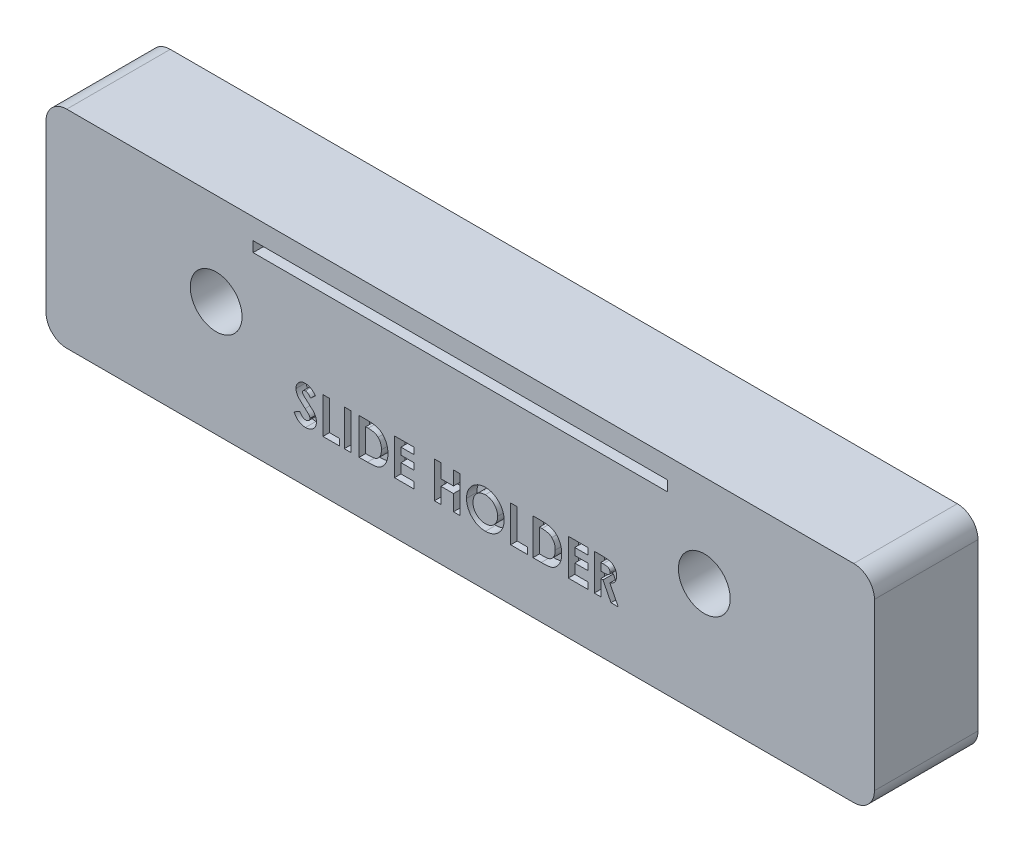
SolidWorks part; units mm, degrees
ref_plane "Front Plane" through (0, 0, 0) normal (0, 0, 1) x (1, 0, 0)
ref_plane "Top Plane" through (0, 0, 0) normal (0, 1, 0) x (1, 0, 0)
ref_plane "Right Plane" through (0, 0, 0) normal (1, 0, 0) x (0, 0, -1)
sketch "Sketch1" plane through (0, 0, 0) normal (0, 0, 1) x (1, 0, 0)
  line L1 (-40.3722, 21.485) -> (39.6278, 21.485)
  line L2 (-40.3722, 21.485) -> (-40.3722, 1.485)
  line L3 (-40.3722, 1.485) -> (39.6278, 1.485)
  line L4 (39.6278, 21.485) -> (39.6278, 1.485)
  dimension "D1" = 80
  dimension "D2" = 20
extrude "Boss-Extrude1" add sketch "Sketch1" along normal blind 10
sketch "Sketch2" plane through (0, 0, 10) normal (0, 0, 1) x (1, 0, 0)
  line L0 (39.6278, 21.485) -> (-40.3722, 21.485) construction
  line L1 (-40.3722, 21.485) -> (-40.3722, 1.485) construction
  line L2 (-0.3722, 21.485) -> (-0.3722, 1.485) construction
  line L3 (-40.3722, 1.485) -> (39.6278, 1.485) construction
  circle A0 centre (-23.9422, 12.585) radius 2.5
  circle A1 centre (23.1978, 12.585) radius 2.5
  dimension "D1" = 5
  dimension "D2" = 8.9
  dimension "D3" = 16.43
extrude "Cut-Extrude1" cut sketch "Sketch2" against normal blind 10
sketch "Sketch3" plane through (0, 0, 10) normal (0, 0, 1) x (1, 0, 0)
  line L0 (39.6278, 21.485) -> (-40.3722, 21.485) construction
  line L1 (-20.3722, 19.485) -> (19.6278, 19.485)
  line L2 (-20.3722, 19.485) -> (-20.3722, 18.485)
  line L3 (-20.3722, 18.485) -> (19.6278, 18.485)
  line L4 (19.6278, 19.485) -> (19.6278, 18.485)
  point P6 (-0.3722, 19.485)
  point P7 (-0.3722, 21.485)
  dimension "D1" = 1
  dimension "D2" = 2
  dimension "D3" = 40
extrude "Cut-Extrude2" cut sketch "Sketch3" against normal through all
sketch "Sketch4" plane through (0, 0, 10) normal (0, 0, 1) x (1, 0, 0)
  line L0 (-40.3722, 6.485) -> (39.6278, 6.485) construction
  line L1 (-40.3722, 21.485) -> (-40.3722, 1.485) construction
  line L3 (-40.3722, 1.485) -> (39.6278, 1.485) construction
  line L4 (39.6278, 1.485) -> (39.6278, 21.485) construction
  text T0 "<b>SLIDE HOLDER</b>"
  point P5 (36.3653, 8.1854)
  point P9 (-40.3722, 11.485)
  point P10 (0, 0)
  point P11 (0, 0)
  dimension "D1" = 5
extrude "Cut-Extrude3" cut sketch "Sketch4" against normal blind 1
fillet "Fillet1" radius 2 4 edges at (39.6278, 21.485, 5) (39.6278, 1.485, 5) (-40.3722, 1.485, 5) (-40.3722, 21.485, 5)
